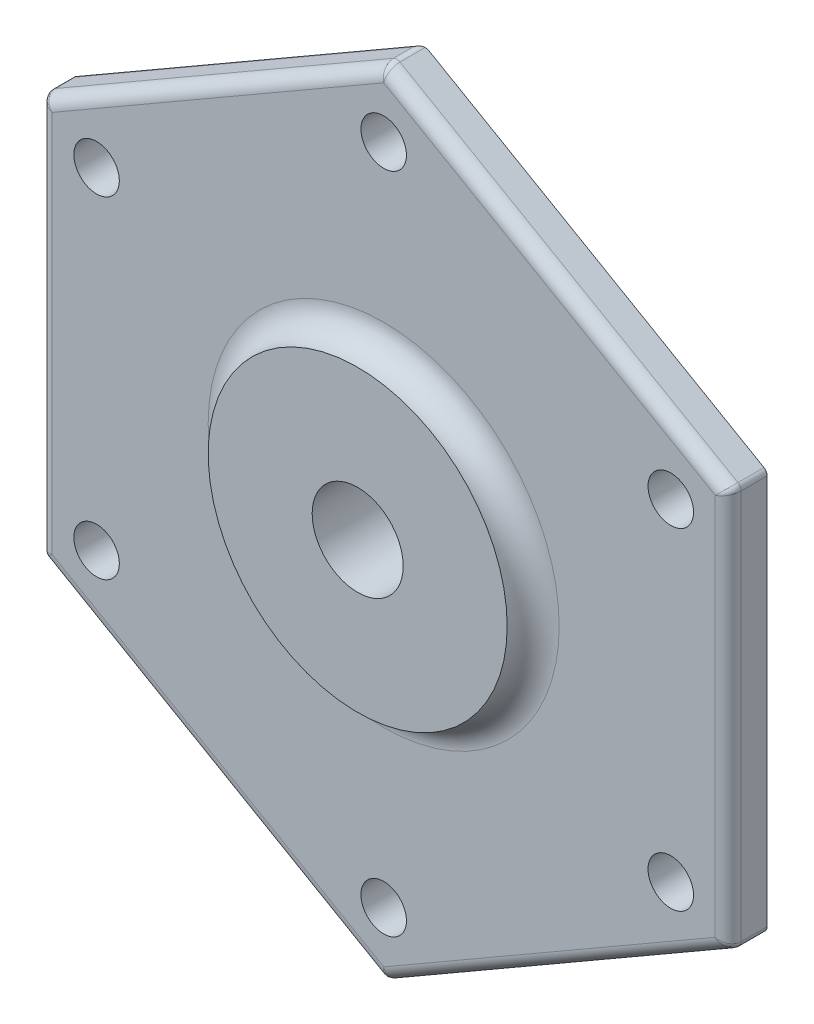
SolidWorks part; units mm, degrees
ref_plane "Front Plane" through (0, 0, 0) normal (0, 0, 1) x (1, 0, 0)
ref_plane "Top Plane" through (0, 0, 0) normal (0, 1, 0) x (1, 0, 0)
ref_plane "Right Plane" through (0, 0, 0) normal (1, 0, 0) x (0, 0, -1)
sketch "Sketch1" plane through (0, 0, 0) normal (0, 0, 1) x (1, 0, 0)
  line L1 (-53, -30.5996) -> (0, -61.1991)
  line L2 (0, -61.1991) -> (53, -30.5996)
  line L3 (53, -30.5996) -> (53, 30.5996)
  line L4 (53, 30.5996) -> (0, 61.1991)
  line L5 (0, 61.1991) -> (-53, 30.5996)
  line L6 (-53, 30.5996) -> (-53, -30.5996)
  circle A0 centre (0, 0) radius 53 construction
  circle A1 centre (0, 51) radius 3.5
  circle A2 centre (44.1673, 25.5) radius 3.5
  circle A3 centre (44.1673, -25.5) radius 3.5
  circle A4 centre (0, -51) radius 3.5
  circle A5 centre (-44.1673, -25.5) radius 3.5
  circle A6 centre (-44.1673, 25.5) radius 3.5
  circle A7 centre (0, 0) radius 7
  circle A8 centre (0, 0) radius 51 construction
  point P23 (0, 0)
  point P24 (0, 0)
  point P25 (0, 0)
  dimension "D2" = 7
  dimension "D4" = 14
  dimension "D5" = 102
  dimension "D1" = 106
  dimension "D3" = 6
extrude "Boss-Extrude1" add sketch "Sketch1" along normal blind 16
sketch "Sketch3" plane through (0, 0, 16) normal (0, 0, 1) x (1, 0, 0)
  line L0 (-53, 30.5996) -> (-53, -30.5996) construction
  line L1 (-53, -30.5996) -> (0, -61.1991) construction
  line L2 (0, -61.1991) -> (53, -30.5996) construction
  line L3 (53, -30.5996) -> (53, 30.5996) construction
  line L4 (53, 30.5996) -> (0, 61.1991) construction
  line L5 (0, 61.1991) -> (-53, 30.5996) construction
  line L6 (-53, 30.5996) -> (-53, -30.5996)
  line L7 (-53, -30.5996) -> (0, -61.1991)
  line L8 (0, -61.1991) -> (53, -30.5996)
  line L9 (53, -30.5996) -> (53, 30.5996)
  line L10 (53, 30.5996) -> (0, 61.1991)
  line L11 (0, 61.1991) -> (-53, 30.5996)
  circle A0 centre (0, 0) radius 23
  dimension "D1" = 46
extrude "Cut-Extrude1" cut sketch "Sketch3" against normal blind 4
sketch "Sketch4" plane through (0, 0, 0) normal (0, 0, -1) x (-1, 0, 0)
  line L0 (-53, 30.5996) -> (0, 61.1991) construction
  line L1 (-53, -30.5996) -> (-53, 30.5996) construction
  line L2 (0, -61.1991) -> (-53, -30.5996) construction
  line L3 (53, -30.5996) -> (0, -61.1991) construction
  line L4 (53, 30.5996) -> (53, -30.5996) construction
  line L5 (0, 61.1991) -> (53, 30.5996) construction
  line L6 (-53, -30.5996) -> (-53, 30.5996)
  line L7 (0, -61.1991) -> (-53, -30.5996)
  line L8 (53, -30.5996) -> (0, -61.1991)
  line L9 (53, 30.5996) -> (53, -30.5996)
  line L10 (0, 61.1991) -> (53, 30.5996)
  line L11 (-53, 30.5996) -> (0, 61.1991)
  circle A0 centre (0, 0) radius 45
  circle A1 centre (0, 0) radius 40
  circle A2 centre (0, 0) radius 19
  circle A3 centre (0, 0) radius 14
  line M1 (53, -30.5996) -> (53, 30.5996)
  line M2 (53, 30.5996) -> (0, 61.1991)
  line M3 (0, 61.1991) -> (-53, 30.5996)
  line M4 (-53, 30.5996) -> (-53, -30.5996)
  line M5 (-53, -30.5996) -> (0, -61.1991)
  line M6 (0, -61.1991) -> (53, -30.5996)
  circle M7 centre (0, 51) radius 3.5
  circle M8 centre (0, 0) radius 7
  circle M9 centre (-44.1673, 25.5) radius 3.5
  circle M10 centre (-44.1673, -25.5) radius 3.5
  circle M11 centre (0, -51) radius 3.5
  circle M12 centre (44.1673, -25.5) radius 3.5
  circle M13 centre (44.1673, 25.5) radius 3.5
  dimension "D1" = 90
  dimension "D2" = 80
  dimension "D3" = 38
  dimension "D4" = 28
extrude "Cut-Extrude2" cut sketch "Sketch4" against normal blind 6 contours A0 M6 M1 M2 M3 M4 M5 M7 M9 M11 M13 M12 M10 | A1 A2 | A3 M8 region at (51.3808, 0, 0) region at (38.8686, 0, 0) region at (13.604, 0, 0)
fillet "Fillet1" radius 4 1 edges at (23, 0, 12)
fillet "Fillet2" radius 2 8 edges at (-19, 0, 6) (-40, 0, 6) (-26.5, 45.8993, 12) (-53, 0, 12) (-26.5, -45.8993, 12) (26.5, -45.8993, 12) (53, 0, 12) (26.5, 45.8993, 12)
chamfer "Chamfer1" distance 1 angle 45 1 edges at (-45, 0, 0)
fillet "Fillet4" radius 1 13 edges at (0, 60.5227, 11.4142) (-52.4142, 30.2614, 11.4142) (52.4142, 30.2614, 11.4142) (52.4142, -30.2614, 11.4142) (0, -60.5227, 11.4142) (-52.4142, -30.2614, 11.4142) (-26.5, 45.8993, 6) (0, 61.1991, 8) (-53, 30.5996, 8) (53, 30.5996, 8) (53, -30.5996, 8) (0, -61.1991, 8) (-53, -30.5996, 8)
